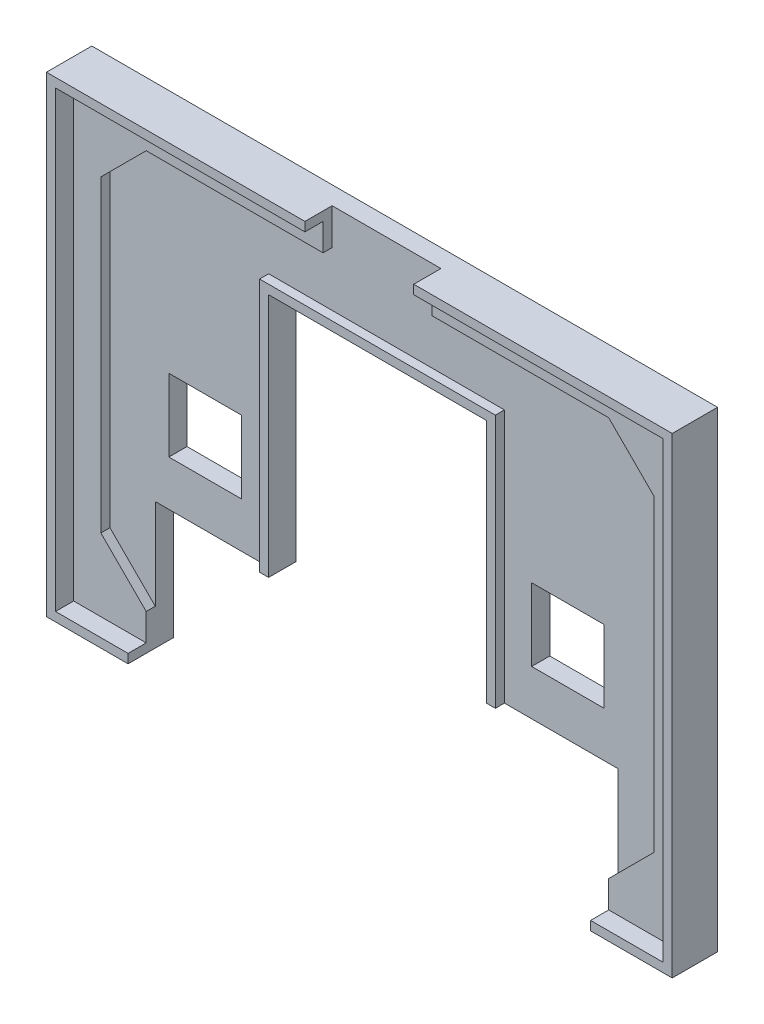
SolidWorks part; units mm, degrees
ref_plane "Přední rovina" through (0, 0, 0) normal (0, 0, 1) x (1, 0, 0)
ref_plane "Horní rovina" through (0, 0, 0) normal (0, 1, 0) x (1, 0, 0)
ref_plane "Pravá rovina" through (0, 0, 0) normal (1, 0, 0) x (0, 0, -1)
sketch "Skica1" plane through (0, 0, 0) normal (0, 0, 1) x (1, 0, 0)
  line L1 (-33.5, -25) -> (33.5, -25)
  line L2 (-33.5, -25) -> (-33.5, 25)
  line L3 (-33.5, 25) -> (33.5, 25)
  line L4 (33.5, -25) -> (33.5, 25)
  line L5 (-33.5, -25) -> (33.5, 25) construction
  line L6 (-33.5, 25) -> (33.5, -25) construction
  point P0 (0, 0)
  dimension "D1" = 67
  dimension "D2" = 50
extrude "Přidat vysunutím1" add sketch "Skica1" along normal blind 3
sketch "Skica2" plane through (0, 0, 3) normal (0, 0, 1) x (1, 0, 0)
  line L0 (-1000, 0) -> (49000, 0) construction
  line L1 (0, -1000) -> (0, 49000) construction
  line L2 (-1000, -22) -> (49000, -22) construction
  line L3 (-25.5, -1000) -> (-25.5, 49000) construction
  line L4 (-30.5, -1000) -> (-30.5, 49000) construction
  line L6 (-33.5, -25) -> (33.5, -25) construction
  line L7 (-25.5, -22) -> (-30.5, -17)
  line L8 (-30.5, -17) -> (-30.5, 17)
  line L9 (-25.5, -22) -> (25.5, -22)
  line L10 (30.5, -17) -> (30.5, 17)
  line L11 (25.5, -22) -> (30.5, -17)
  line L12 (25.5, 22) -> (30.5, 17)
  line L13 (-25.5, 22) -> (25.5, 22)
  line L14 (-25.5, 22) -> (-30.5, 17)
  point P20 (0, -22)
  point P21 (30.5, 0)
  point P24 (-30.5, 0)
  dimension "D1" = 30.5
  dimension "D2" = 5
  dimension "D3" = 3
  dimension "D4" = 45
extrude "Odebrat vysunutím1" cut sketch "Skica2" against normal offset from surface (1 mm away) 2 up to face at (0, 0, 0)
sketch "Skica3" plane through (0, 0, 0) normal (0, 0, -1) x (-1, 0, 0)
  line L0 (0, -1000) -> (0, 49000) construction
  line L1 (33.5, -25) -> (-33.5, -25) construction
  line L2 (24, 1) -> (16, 1)
  line L3 (24, 1) -> (24, -7)
  line L4 (24, -7) -> (16, -7)
  line L5 (16, 1) -> (16, -7)
  line L6 (-16, 1) -> (-16, -7)
  line L7 (33.5, -25) -> (-33.5, -25) construction
  line L8 (25.5, -25) -> (-25.5, -25)
  line L9 (25.5, -25) -> (25.5, -12)
  line L11 (-25.5, -25) -> (-25.5, -12)
  line L12 (-24, -7) -> (-16, -7)
  line L13 (25.5, -12) -> (12, -12)
  line L15 (12, -12) -> (12, 15)
  line L16 (12, 15) -> (-12, 15)
  line L17 (-12, -12) -> (-12, 15)
  line L18 (-12, -12) -> (-25.5, -12)
  line L19 (-24, 1) -> (-24, -7)
  line L20 (-24, 1) -> (-16, 1)
  dimension "D1" = 16
  dimension "D2" = 8
  dimension "D3" = 18
  dimension "D4" = 13
  dimension "D5" = 51
  dimension "D6" = 24
  dimension "D7" = 27
extrude "Odebrat vysunutím2" cut sketch "Skica3" against normal through all
sketch "Skica4" plane through (0, 0, 2) normal (0, 0, 1) x (1, 0, 0)
  line L0 (12, 15) -> (12, -12) construction
  line L1 (-12, -12) -> (-12, 15) construction
  line L2 (-12, 15) -> (12, 15) construction
  line L3 (12, 15) -> (12, -12)
  line L4 (-12, -12) -> (-12, 15)
  line L5 (-12, 15) -> (12, 15)
extrude "Vysunout tenkostěnný1" add sketch "Skica4" along normal up to surface (1 mm away) thin up to face at (0, -3.5714, 3) thin type one direction reverse wall 1
sketch "Skica5" plane through (0, 0, 0) normal (0, 0, -1) x (-1, 0, 0)
  line L0 (-33.5, 25) -> (33.5, 25) construction
  line L1 (33.5, 25) -> (33.5, -25) construction
  line L2 (33.5, -25) -> (25.5, -25) construction
  line L3 (-33.5, -25) -> (-33.5, 25) construction
  line L4 (-25.5, -25) -> (-33.5, -25) construction
  line L5 (-33.5, 25) -> (33.5, 25)
  line L6 (33.5, 25) -> (33.5, -25)
  line L7 (33.5, -25) -> (25.5, -25)
  line L8 (-33.5, -25) -> (-33.5, 25)
  line L9 (-25.5, -25) -> (-33.5, -25)
extrude "Vysunout tenkostěnný2" add sketch "Skica5" against normal blind 5 thin thin type one direction reverse wall 1
sketch "Skica6" plane through (0, 0, 2) normal (0, 0, 1) x (1, 0, 0)
  line L0 (0, -1000) -> (0, 49000) construction
  line L1 (25.5, 22) -> (-25.5, 22) construction
  line L2 (-6, 22) -> (6, 22)
  line L3 (-6, 22) -> (-6, 26)
  line L4 (-6, 26) -> (6, 26)
  line L5 (6, 22) -> (6, 26)
  line L6 (34.5, 26) -> (-34.5, 26) construction
  dimension "D1" = 12
extrude "Odebrat vysunutím3" cut sketch "Skica6" along normal through all
sketch "Skica7" plane through (0, 0, 0) normal (0, 0, -1) x (-1, 0, 0)
  line L0 (-28.9698, 21.7674) -> (-27.3747, 21.7674)
  line L1 (-27.3747, 21.7674) -> (-27.3747, 20.2225)
  line L2 (-27.3747, 20.2225) -> (-26.0283, 20.2225)
  line L3 (-26.0283, 20.2225) -> (-26.0283, 18.9916)
  line L4 (-26.0283, 18.9916) -> (-20.5606, 18.9916)
  line L6 (-19.0893, 13.2881) -> (-27.4995, 13.2881)
  line L7 (-27.4995, 13.2881) -> (-27.4995, 11.8247)
  line L8 (-27.4995, 11.8247) -> (-26.0283, 11.8247)
  line L9 (-26.0283, 11.8247) -> (-26.0283, 10.4217)
  line L10 (-26.0283, 10.4217) -> (-24.599, 10.4217)
  line L11 (-24.599, 10.4217) -> (-24.599, 9.0294)
  line L12 (-24.599, 9.0294) -> (-26.0283, 9.0294)
  line L13 (-26.0283, 9.0294) -> (-26.0283, 10.4117)
  line L16 (-27.5095, 11.8147) -> (-28.9698, 11.8147)
  line L17 (-28.9698, 11.8147) -> (-28.9698, 14.6619)
  line L18 (-28.9698, 14.6619) -> (-30.2742, 14.6619)
  line L19 (-30.2742, 14.6619) -> (-30.2742, 11.8147)
  line L20 (-30.2742, 11.8147) -> (-31.8629, 11.8147)
  line L21 (-31.8629, 11.8147) -> (-31.8629, 16.1399)
  line L22 (-31.8629, 16.1399) -> (-30.4599, 16.1399)
  line L23 (-30.4599, 16.1399) -> (-30.4599, 17.6535)
  line L24 (-30.4599, 17.6535) -> (-28.9698, 17.6535)
  line L29 (-27.5095, 11.8147) -> (-27.5095, 10.4117)
  line L30 (-27.5095, 10.4117) -> (-26.0283, 10.4117)
  line L31 (-28.9698, 17.6535) -> (-28.9698, 18.9916)
  line L32 (-28.9698, 18.9916) -> (-27.3747, 18.9916)
  line L33 (-27.3747, 18.9916) -> (-27.3747, 20.2125)
  line L34 (-27.3747, 20.2125) -> (-28.9698, 20.2125)
  line L36 (-34.5, -26) -> (-34.5, 26) construction
  line L37 (-19.2141, 20.2125) -> (-17.6191, 20.2125)
  line L38 (-19.2141, 18.9916) -> (-19.2141, 20.2125)
  line L39 (-17.6191, 18.9916) -> (-19.2141, 18.9916)
  line L40 (-17.6191, 17.6535) -> (-17.6191, 18.9916)
  line L41 (-16.129, 17.6535) -> (-17.6191, 17.6535)
  line L42 (-16.129, 16.1399) -> (-16.129, 17.6535)
  line L43 (-14.726, 16.1399) -> (-16.129, 16.1399)
  line L44 (-14.726, 11.8147) -> (-14.726, 16.1399)
  line L45 (-16.3146, 11.8147) -> (-14.726, 11.8147)
  line L46 (-16.3146, 14.6619) -> (-16.3146, 11.8147)
  line L47 (-17.6191, 14.6619) -> (-16.3146, 14.6619)
  line L48 (-17.6191, 11.8147) -> (-17.6191, 14.6619)
  line L49 (-19.0793, 11.8147) -> (-17.6191, 11.8147)
  line L50 (-19.0793, 11.8147) -> (-19.0793, 10.4117)
  line L51 (-19.0793, 10.4117) -> (-20.5606, 10.4117)
  line L52 (-20.5606, 9.0294) -> (-20.5606, 10.4117)
  line L53 (-21.9899, 9.0294) -> (-20.5606, 9.0294)
  line L54 (-21.9899, 10.4217) -> (-21.9899, 9.0294)
  line L55 (-20.5606, 10.4217) -> (-21.9899, 10.4217)
  line L56 (-20.5606, 11.8247) -> (-20.5606, 10.4217)
  line L57 (-19.0893, 11.8247) -> (-20.5606, 11.8247)
  line L58 (-19.0893, 13.2881) -> (-19.0893, 11.8247)
  line L59 (-20.5606, 20.2225) -> (-20.5606, 18.9916)
  line L60 (-19.2141, 20.2225) -> (-20.5606, 20.2225)
  line L61 (-19.2141, 21.7674) -> (-19.2141, 20.2225)
  line L62 (-17.6191, 21.7674) -> (-19.2141, 21.7674)
  line L65 (-25.5, -26) -> (-34.5, -26) construction
  line L66 (-28.9698, 20.2125) -> (-28.9698, 21.7674)
  line L67 (-17.6191, 21.7674) -> (-17.6191, 20.2125)
  line L68 (34.5, 26) -> (34.5, -26) construction
  line L69 (34.5, -26) -> (25.5, -26) construction
  line L70 (0, 0) -> (0, 36.3829) construction
  line L71 (17.6191, 21.7674) -> (19.2141, 21.7674)
  line L72 (19.2141, 21.7674) -> (19.2141, 20.2225)
  line L73 (19.2141, 20.2225) -> (20.5606, 20.2225)
  line L74 (20.5606, 20.2225) -> (20.5606, 18.9916)
  line L75 (26.0283, 18.9916) -> (20.5606, 18.9916)
  line L76 (26.0283, 20.2225) -> (26.0283, 18.9916)
  line L77 (27.3747, 20.2225) -> (26.0283, 20.2225)
  line L78 (27.3747, 21.7674) -> (27.3747, 20.2225)
  line L79 (28.9698, 21.7674) -> (27.3747, 21.7674)
  line L80 (28.9698, 20.2125) -> (28.9698, 21.7674)
  line L81 (27.3747, 20.2125) -> (28.9698, 20.2125)
  line L82 (27.3747, 18.9916) -> (27.3747, 20.2125)
  line L83 (28.9698, 18.9916) -> (27.3747, 18.9916)
  line L84 (28.9698, 17.6535) -> (28.9698, 18.9916)
  line L85 (30.4599, 17.6535) -> (28.9698, 17.6535)
  line L86 (30.4599, 16.1399) -> (30.4599, 17.6535)
  line L87 (31.8629, 16.1399) -> (30.4599, 16.1399)
  line L88 (31.8629, 11.8147) -> (31.8629, 16.1399)
  line L89 (30.2742, 11.8147) -> (31.8629, 11.8147)
  line L90 (30.2742, 14.6619) -> (30.2742, 11.8147)
  line L91 (28.9698, 14.6619) -> (30.2742, 14.6619)
  line L92 (28.9698, 11.8147) -> (28.9698, 14.6619)
  line L93 (27.5095, 11.8147) -> (28.9698, 11.8147)
  line L94 (27.5095, 11.8147) -> (27.5095, 10.4117)
  line L95 (27.5095, 10.4117) -> (26.0283, 10.4117)
  line L96 (26.0283, 9.0294) -> (26.0283, 10.4117)
  line L97 (24.599, 9.0294) -> (26.0283, 9.0294)
  line L98 (24.599, 10.4217) -> (24.599, 9.0294)
  line L99 (26.0283, 10.4217) -> (24.599, 10.4217)
  line L100 (26.0283, 11.8247) -> (26.0283, 10.4217)
  line L101 (27.4995, 11.8247) -> (26.0283, 11.8247)
  line L102 (27.4995, 13.2881) -> (27.4995, 11.8247)
  line L103 (19.0893, 13.2881) -> (27.4995, 13.2881)
  line L104 (19.0893, 13.2881) -> (19.0893, 11.8247)
  line L105 (19.0893, 11.8247) -> (20.5606, 11.8247)
  line L106 (20.5606, 11.8247) -> (20.5606, 10.4217)
  line L107 (20.5606, 10.4217) -> (21.9899, 10.4217)
  line L108 (21.9899, 10.4217) -> (21.9899, 9.0294)
  line L109 (21.9899, 9.0294) -> (20.5606, 9.0294)
  line L110 (20.5606, 9.0294) -> (20.5606, 10.4117)
  line L111 (19.0793, 10.4117) -> (20.5606, 10.4117)
  line L112 (19.0793, 11.8147) -> (19.0793, 10.4117)
  line L113 (19.0793, 11.8147) -> (17.6191, 11.8147)
  line L114 (17.6191, 11.8147) -> (17.6191, 14.6619)
  line L115 (17.6191, 14.6619) -> (16.3146, 14.6619)
  line L116 (16.3146, 14.6619) -> (16.3146, 11.8147)
  line L117 (16.3146, 11.8147) -> (14.726, 11.8147)
  line L118 (14.726, 11.8147) -> (14.726, 16.1399)
  line L119 (14.726, 16.1399) -> (16.129, 16.1399)
  line L120 (16.129, 16.1399) -> (16.129, 17.6535)
  line L121 (16.129, 17.6535) -> (17.6191, 17.6535)
  line L122 (17.6191, 17.6535) -> (17.6191, 18.9916)
  line L123 (17.6191, 18.9916) -> (19.2141, 18.9916)
  line L124 (19.2141, 18.9916) -> (19.2141, 20.2125)
  line L125 (19.2141, 20.2125) -> (17.6191, 20.2125)
  line L126 (17.6191, 21.7674) -> (17.6191, 20.2125)
  dimension "D1" = 49.226
  dimension "D2" = 50.629
  dimension "D3" = 50.8146
  dimension "D4" = 52.1191
  dimension "D5" = 53.5793
  dimension "D6" = 53.5893
  dimension "D7" = 53.7141
  dimension "D8" = 55.0606
  dimension "D9" = 56.4899
  dimension "D10" = 59.099
  dimension "D11" = 35.0294
  dimension "D12" = 36.4117
  dimension "D13" = 36.4217
  dimension "D14" = 40.6619
  dimension "D15" = 42.1399
  dimension "D16" = 39.2881
  dimension "D17" = 43.6535
  dimension "D18" = 44.9916
  dimension "D19" = 46.2225
  dimension "D21" = 46.2125
  dimension "D23" = 47.7674
extrude "Odebrat vysunutím4" cut sketch "Skica7" against normal blind 1
sketch "Skica8" plane through (0, 0, 1) normal (0, 0, -1) x (-1, 0, 0)
  line L0 (-28.9698, 17.6535) -> (-30.4599, 17.6535) construction
  line L1 (-27.3747, 17.6535) -> (-24.5747, 17.6535)
  line L2 (-27.3747, 17.6535) -> (-27.3747, 16.1399)
  line L3 (-27.3747, 16.1399) -> (-24.5747, 16.1399)
  line L4 (-24.5747, 17.6535) -> (-24.5747, 16.1399)
  line L5 (-27.3747, 20.2125) -> (-27.3747, 18.9916) construction
  line L6 (-30.4599, 16.1399) -> (-31.8629, 16.1399) construction
  line L7 (-23.2944, 13.2881) -> (-23.2944, 21.2228) construction
  line L8 (-27.4995, 13.2881) -> (-19.0893, 13.2881) construction
  line L9 (-19.2141, 16.1399) -> (-22.0141, 16.1399)
  line L10 (-22.0141, 17.6535) -> (-22.0141, 16.1399)
  line L11 (-19.2141, 17.6535) -> (-22.0141, 17.6535)
  line L12 (-19.2141, 17.6535) -> (-19.2141, 16.1399)
  line L13 (0, 0) -> (0, 32.7031) construction
  line L14 (19.2141, 17.6535) -> (19.2141, 16.1399)
  line L15 (19.2141, 17.6535) -> (22.0141, 17.6535)
  line L16 (22.0141, 17.6535) -> (22.0141, 16.1399)
  line L17 (19.2141, 16.1399) -> (22.0141, 16.1399)
  line L18 (27.3747, 16.1399) -> (24.5747, 16.1399)
  line L19 (24.5747, 17.6535) -> (24.5747, 16.1399)
  line L20 (27.3747, 17.6535) -> (24.5747, 17.6535)
  line L21 (27.3747, 17.6535) -> (27.3747, 16.1399)
  point P4 (-25.9747, 17.6535)
  dimension "D1" = 0
  dimension "D2" = 0
  dimension "D3" = 0
  dimension "D4" = 2.8
extrude "Přidat vysunutím2" add sketch "Skica8" along normal blind 1
sketch "Skica9" plane through (0, 0, 0) normal (0, 0, -1) x (-1, 0, 0)
  line L0 (-31.8629, 16.1399) -> (-31.8629, 11.8147) construction
  line L1 (-26.0283, 9.0294) -> (-24.599, 9.0294) construction
  text T0 "MART" font "BLOXAT" height 5.8
  dimension "D1" = 20.7338
  dimension "D2" = 8.5575
extrude "Odebrat vysunutím5" cut sketch "Skica9" against normal blind 1
